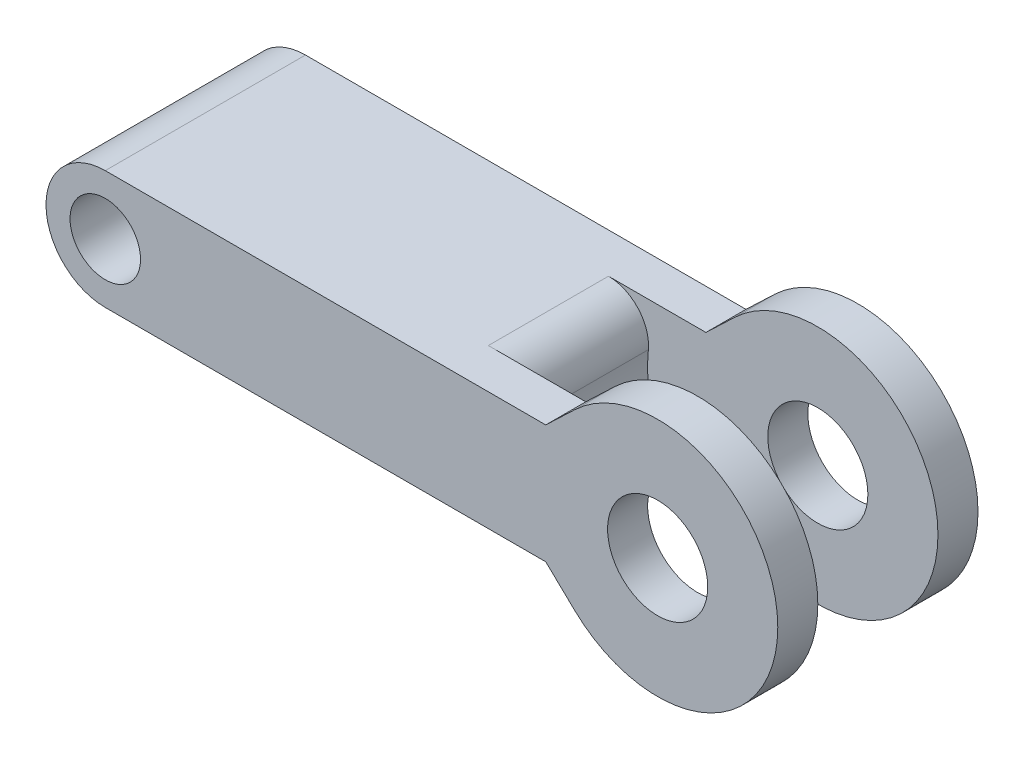
SolidWorks part; units mm, degrees
ref_plane "Front Plane" through (0, 0, 0) normal (0, 0, 1) x (1, 0, 0)
ref_plane "Top Plane" through (0, 0, 0) normal (0, 1, 0) x (1, 0, 0)
ref_plane "Right Plane" through (0, 0, 0) normal (1, 0, 0) x (0, 0, -1)
sketch "Sketch1" plane through (0, 0, 0) normal (0, 0, 1) x (1, 0, 0)
  line L0 (-27.5891, 2.96) -> (-5.5891, 2.96)
  line L1 (-5.5891, 2.96) -> (-4.1422, 4.3407)
  line L2 (-4.1422, -4.3407) -> (-5.5891, -2.96)
  line L3 (-5.5891, -2.96) -> (-27.5891, -2.96)
  circle A0 centre (0, 0) radius 2.5
  circle A1 centre (0, 0) radius 8.5
  arc A2 (-4.1422, 4.3407) -> (-4.1422, -4.3407) centre (0, 0) cw
  arc A3 (-27.5891, 2.96) -> (-27.5891, -2.96) centre (-27.5891, 0) ccw
  circle A4 centre (-27.5891, 0) radius 1.76
  dimension "D1" = 5
  dimension "D2" = 17
  dimension "D3" = 6
  dimension "D4" = 3.52
  dimension "D5" = 1.2
  dimension "D6" = 2
  dimension "D7" = 22
extrude "Boss-Extrude1" add sketch "Sketch1" along normal blind 5 and the other way blind 5 contours L0 A3 L3 A1 A4 | A2 L1 L0 A1 L3 L2 A0 region at (-18.4317, 0, 0) region at (-6.7785, 2.7718, 0)
extrude "Cut-Extrude1" cut sketch "Sketch1<4>" against normal blind 3 and the other way blind 3 contours L1 A2 L2 L3 A1 L0 | A2 L1 L0 A1 L3 L2 A0 region at (1.4618, 8.133, 0) region at (-6.7785, 2.7718, 0)
sketch "Sketch1<4>" plane through (0, 0, 0) normal (0, 0, 1) x (1, 0, 0) same geometry as "Sketch1"
fillet "Fillet1" radius 2 2 edges at (-7.968, 2.96, 0) (-7.968, -2.96, 0)
